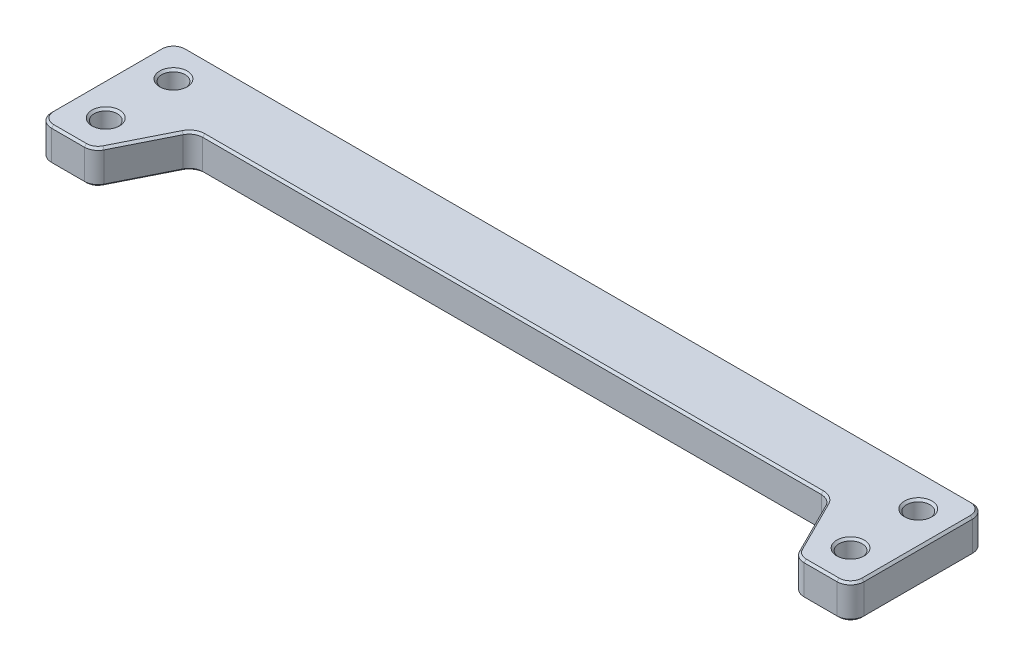
SolidWorks part; units mm, degrees
ref_plane "Front Plane" through (0, 0, 0) normal (0, 0, 1) x (1, 0, 0)
ref_plane "Top Plane" through (0, 0, 0) normal (0, 1, 0) x (1, 0, 0)
ref_plane "Right Plane" through (0, 0, 0) normal (1, 0, 0) x (0, 0, -1)
sketch "Sketch1" plane through (0, 0, 0) normal (0, 1, 0) x (1, 0, 0)
  line L0 (-3.81, 19.05) -> (143.51, 19.05)
  line L1 (146.05, 16.51) -> (146.05, -3.81)
  line L2 (143.51, -6.35) -> (137.3453, -6.35)
  line L3 (135.0734, -4.9459) -> (130.1275, 4.9459)
  line L4 (127.8557, 6.35) -> (11.8443, 6.35)
  line L5 (9.5725, 4.9459) -> (4.6266, -4.9459)
  line L6 (2.3547, -6.35) -> (-3.81, -6.35)
  line L7 (-6.35, -3.81) -> (-6.35, 16.51)
  circle A0 centre (0, 0) radius 2.1828
  circle A1 centre (0, 12.7) radius 2.1828
  circle A2 centre (139.7, 12.7) radius 2.1828
  circle A3 centre (139.7, 0) radius 2.1828
  arc A4 (130.1275, 4.9459) -> (127.8557, 6.35) centre (127.8557, 3.81) ccw
  arc A5 (137.3453, -6.35) -> (135.0734, -4.9459) centre (137.3453, -3.81) cw
  arc A6 (146.05, -3.81) -> (143.51, -6.35) centre (143.51, -3.81) cw
  arc A7 (143.51, 19.05) -> (146.05, 16.51) centre (143.51, 16.51) cw
  arc A8 (-3.81, -6.35) -> (-6.35, -3.81) centre (-3.81, -3.81) cw
  arc A9 (-3.81, 19.05) -> (-6.35, 16.51) centre (-3.81, 16.51) ccw
  arc A10 (11.8443, 6.35) -> (9.5725, 4.9459) centre (11.8443, 3.81) ccw
  arc A11 (4.6266, -4.9459) -> (2.3547, -6.35) centre (2.3547, -3.81) cw
  point P19 (129.4255, 6.35)
  point P22 (135.7755, -6.35)
  point P25 (146.05, -6.35)
  point P34 (10.2745, 6.35)
  point P37 (3.9245, -6.35)
  dimension "D1" = 139.7
  dimension "D3" = 4.3656
  dimension "D4" = 4.3656
  dimension "D5" = 4.3656
  dimension "D6" = 4.3656
  dimension "D17" = 2.54
  dimension "D2" = 12.7
  dimension "D7" = 6.35
  dimension "D8" = 6.35
  dimension "D9" = 6.35
  dimension "D10" = 6.35
  dimension "D11" = 6.1647
  dimension "D12" = 12.7
  dimension "D13" = 6.35
  dimension "D14" = 6.35
  dimension "D15" = 6.35
  dimension "D16" = 6.1647
extrude "Boss-Extrude1" add sketch "Sketch1" along normal blind 6.35
chamfer "Chamfer1" distance 0.3969 angle 45 40 edges at (139.7, 0, 2.1828) (139.7, 0, -10.5172) (0, 0, -10.5172) (0, 0, 2.1828) (132.6005, 0, 0) (136.0099, 0, 5.9707) (140.4276, 0, 6.35) (145.3061, 0, 5.6061) (146.05, 0, -6.35) (145.3061, 0, -18.3061) (69.85, 0, -19.05) (-5.6061, 0, -18.3061) (-6.35, 0, -6.35) (-5.6061, 0, 5.6061) (-0.7276, 0, 6.35) (3.6901, 0, 5.9707) (7.0995, 0, 0) (10.509, 0, -5.9707) (69.85, 0, -6.35) (129.191, 0, -5.9707) (139.7, 6.35, 2.1828) (0, 6.35, -10.5172) (69.85, 6.35, -6.35) (10.509, 6.35, -5.9707) (7.0995, 6.35, 0) (3.6901, 6.35, 5.9707) (-0.7276, 6.35, 6.35) (-5.6061, 6.35, 5.6061) (-6.35, 6.35, -6.35) (-5.6061, 6.35, -18.3061) (69.85, 6.35, -19.05) (145.3061, 6.35, -18.3061) (146.05, 6.35, -6.35) (145.3061, 6.35, 5.6061) (140.4276, 6.35, 6.35) (136.0099, 6.35, 5.9707) (132.6005, 6.35, 0) (129.191, 6.35, -5.9707) (0, 6.35, 2.1828) (139.7, 6.35, -10.5172)
